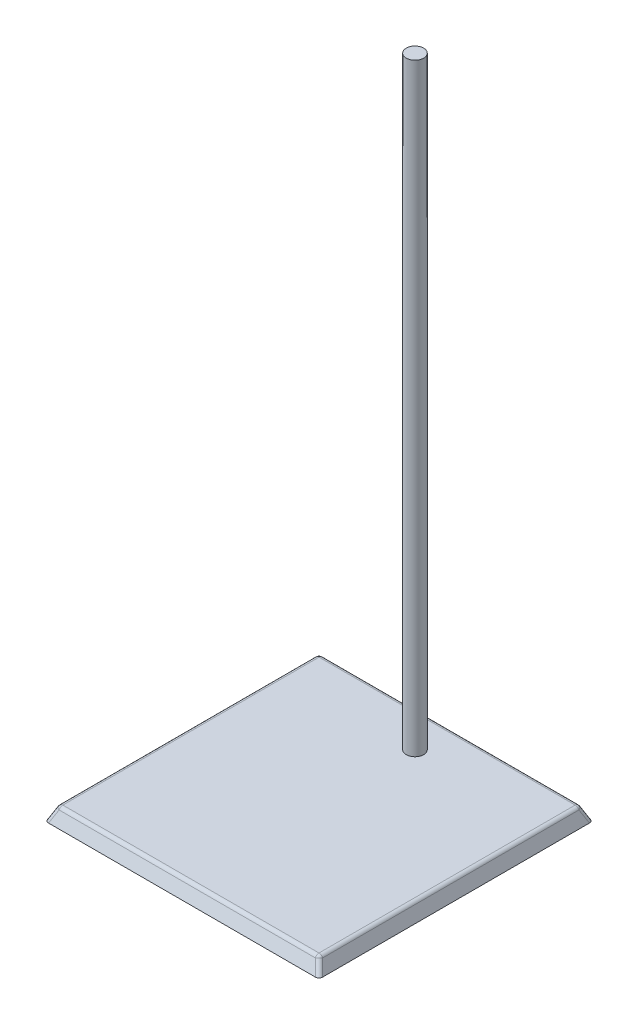
SolidWorks part; units mm, degrees
ref_plane "Front Plane" through (0, 0, 0) normal (0, 0, 1) x (1, 0, 0)
ref_plane "Top Plane" through (0, 0, 0) normal (0, 1, 0) x (1, 0, 0)
ref_plane "Right Plane" through (0, 0, 0) normal (1, 0, 0) x (0, 0, -1)
sketch "Sketch1" plane through (0, 0, 0) normal (0, 1, 0) x (1, 0, 0)
  circle A0 centre (0, 0) radius 6.35
  dimension "D1" = 12.7
extrude "Boss-Extrude1" add sketch "Sketch1" along normal blind 450
sketch "Sketch2" plane through (0, 0, 0) normal (0, 1, 0) x (1, 0, 0)
  line L1 (100, -170) -> (-100, -170)
  line L2 (100, -170) -> (100, 30)
  line L3 (100, 30) -> (-100, 30)
  line L4 (-100, -170) -> (-100, 30)
  line L5 (100, -170) -> (-100, 30) construction
  line L6 (100, 30) -> (-100, -170) construction
  point P0 (0, -70)
  dimension "D1" = 200
  dimension "D2" = 200
  dimension "D3" = 30
extrude "Boss-Extrude2" add sketch "Sketch2" along normal blind 10
chamfer "Chamfer1" distance 10 angle 25 4 edges at (-100, 10, 70) (0, 10, -30) (100, 10, 70) (0, 10, 170) first distance on face at (-100, 5, 70) first distance on face at (0, 5, -30) first distance on face at (100, 5, 70) first distance on face at (0, 5, 170)
fillet "Fillet1" radius 3 8 edges at (-97.6685, 5, -27.6685) (97.6685, 5, -27.6685) (-97.6685, 5, 167.6685) (97.6685, 5, 167.6685) (0, 10, -25.3369) (-95.3369, 10, 70) (0, 10, 165.3369) (95.3369, 10, 70)
equation "\"D1@Boss-Extrude1\"=12in"
